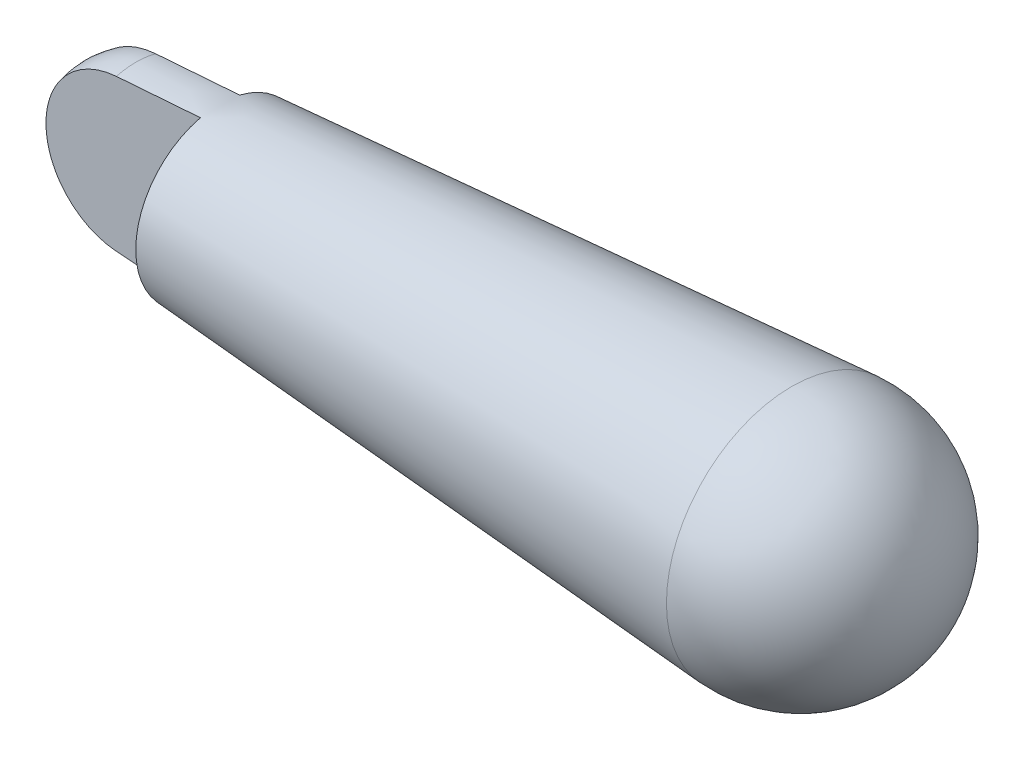
SolidWorks part; units mm, degrees
ref_plane "Front Plane" through (0, 0, 0) normal (0, 0, 1) x (1, 0, 0)
ref_plane "Top Plane" through (0, 0, 0) normal (0, 1, 0) x (1, 0, 0)
ref_plane "Right Plane" through (0, 0, 0) normal (1, 0, 0) x (0, 0, -1)
sketch "Sketch1" plane through (0, 0, 0) normal (0, 0, 1) x (1, 0, 0)
  line L0 (-213.36, 0) -> (213.36, 0)
  line L1 (-264.16, 0) -> (-213.36, 0)
  line L2 (213.36, 0) -> (294.64, 0)
  line L3 (-216.9886, 50.6702) -> (207.5543, 81.0724)
  arc A0 (294.64, 0) -> (207.5543, 81.0724) centre (213.36, 0) ccw
  arc A1 (-216.9886, 50.6702) -> (-264.16, 0) centre (-213.36, 0) ccw
  dimension "D2" = 101.6
  dimension "D3" = 162.56
  dimension "D1" = 426.72
  dimension "D4" = 558.8
  dimension "D5" = 213.36
revolve "Revolve1" add sketch "Sketch1" angle 360 about L0
sketch "Sketch2" plane through (0, 0, 0) normal (0, 1, 0) x (1, 0, 0)
  line L0 (-1000, 0) -> (49000, 0) construction
  line L1 (294.64, -1000) -> (294.64, 49000) construction
  line L2 (-264.16, -1099.3283) -> (-264.16, 48900.6717) construction
  line L10 (-264.16, 139.7) -> (-162.56, 139.7)
  line L11 (-264.16, 139.7) -> (-264.16, 12.7)
  line L12 (-264.16, 12.7) -> (-162.56, 12.7)
  line L13 (-162.56, 139.7) -> (-162.56, 12.7)
  line L14 (-264.16, 139.7) -> (-162.56, 12.7) construction
  line L15 (-264.16, 12.7) -> (-162.56, 139.7) construction
  line L16 (-162.56, -139.7) -> (-162.56, -12.7)
  line L17 (-264.16, -139.7) -> (-162.56, -139.7)
  line L18 (-264.16, -12.7) -> (-162.56, -12.7)
  line L19 (-264.16, -139.7) -> (-264.16, -12.7)
  arc A0 (207.5543, -81.0724) -> (207.5543, 81.0724) centre (213.36, 0) ccw construction
  arc A2 (-216.9886, 50.6702) -> (-216.9886, -50.6702) centre (-213.36, 0) ccw construction
  point P18 (-213.36, 76.2)
  dimension "D1" = 101.6
  dimension "D2" = 127
  dimension "D3" = 12.7
extrude "Cut-Extrude2" cut sketch "Sketch2" against normal blind 157.48 and the other way blind 157.48
sketch3d "3DSketch2"
  line L0 (-264.16, 0, 0) -> (294.64, 0, 0)
  line L1 (-213.36, 0, -190.5) -> (-213.36, 0, 190.5)
  line L2 (213.36, 0, -190.5) -> (213.36, 0, 190.5)
  arc A0 (-216.9886, 50.6702, 0) -> (-264.16, 0, 0) centre (-213.36, 0, 0) ccw construction
  point P3 (-213.36, 0, 0)
  point P4 (213.36, 0, 0)
  point P5 (0, 0, 0)
  point P6 (0, 0, 0)
  point P7 (0, 0, 0)
  point P11 (-213.36, 0, 50.8)
  dimension "D1" = 213.36
  dimension "D2" = 213.36
  dimension "D3" = 381
